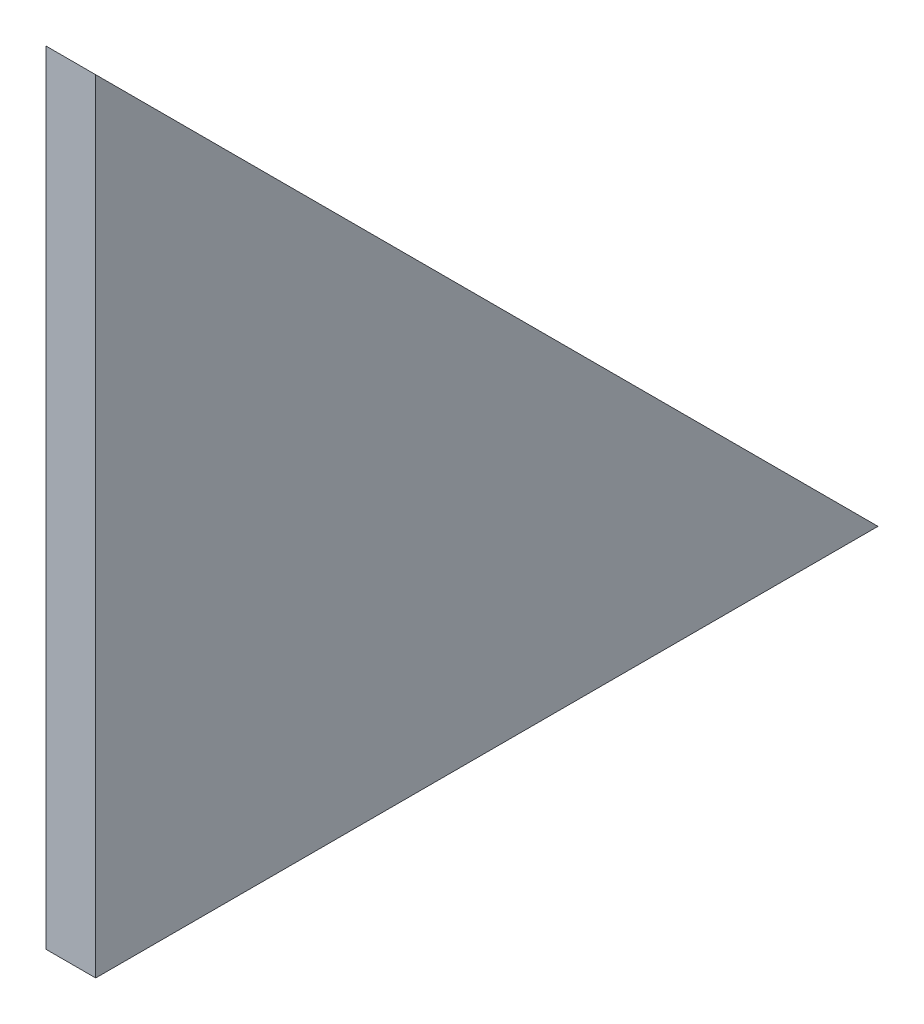
SolidWorks part; units mm, degrees
material "Acero al carbono no aleado"
ref_plane "Alzado" through (0, 0, 0) normal (0, 0, 1) x (1, 0, 0)
ref_plane "Planta" through (0, 0, 0) normal (0, 1, 0) x (1, 0, 0)
ref_plane "Vista lateral" through (0, 0, 0) normal (1, 0, 0) x (0, 0, -1)
sketch "Croquis1" plane through (0, 0, 0) normal (0, 0, 1) x (1, 0, 0)
  line L1 (3.175, -50) -> (-3.175, -50)
  line L2 (3.175, -50) -> (3.175, 50)
  line L3 (3.175, 50) -> (-3.175, 50)
  line L4 (-3.175, -50) -> (-3.175, 50)
  line L5 (3.175, -50) -> (-3.175, 50) construction
  line L6 (3.175, 50) -> (-3.175, -50) construction
  line L8 (3.175, -50) -> (3.175, -47)
  point P0 (0, 0)
  dimension "D1" = 100
  dimension "D3" = 6.35
extrude "Saliente-Extruir1" add sketch "Croquis1" along normal mid plane 100 contours L4 L1 L2 L3
sketch "Croquis2" plane through (3.175, 0, 0) normal (1, 0, 0) x (0, 0, -1)
  line L0 (-50, 50) -> (50, -50)
  line L4 (-50, 50) -> (-50, -50)
  line L5 (-50, -50) -> (50, -50)
  line L6 (50, -50) -> (50, 50)
  line L7 (50, 50) -> (-50, 50)
  line L8 (-50, 50) -> (-50, -50)
  line L10 (50, -50) -> (50, 50)
  line L11 (50, 50) -> (-50, 50)
  line L13 (-50, -50) -> (50, -50)
  line M7 (50, -50) -> (50, 50)
  line M8 (50, 50) -> (-50, 50)
  dimension "D1" = 0
extrude "Cortar-Extruir1" cut sketch "Croquis2" against normal blind 100 contours L0 M8 M7 region at (3.175, 16.6667, -16.6667)
